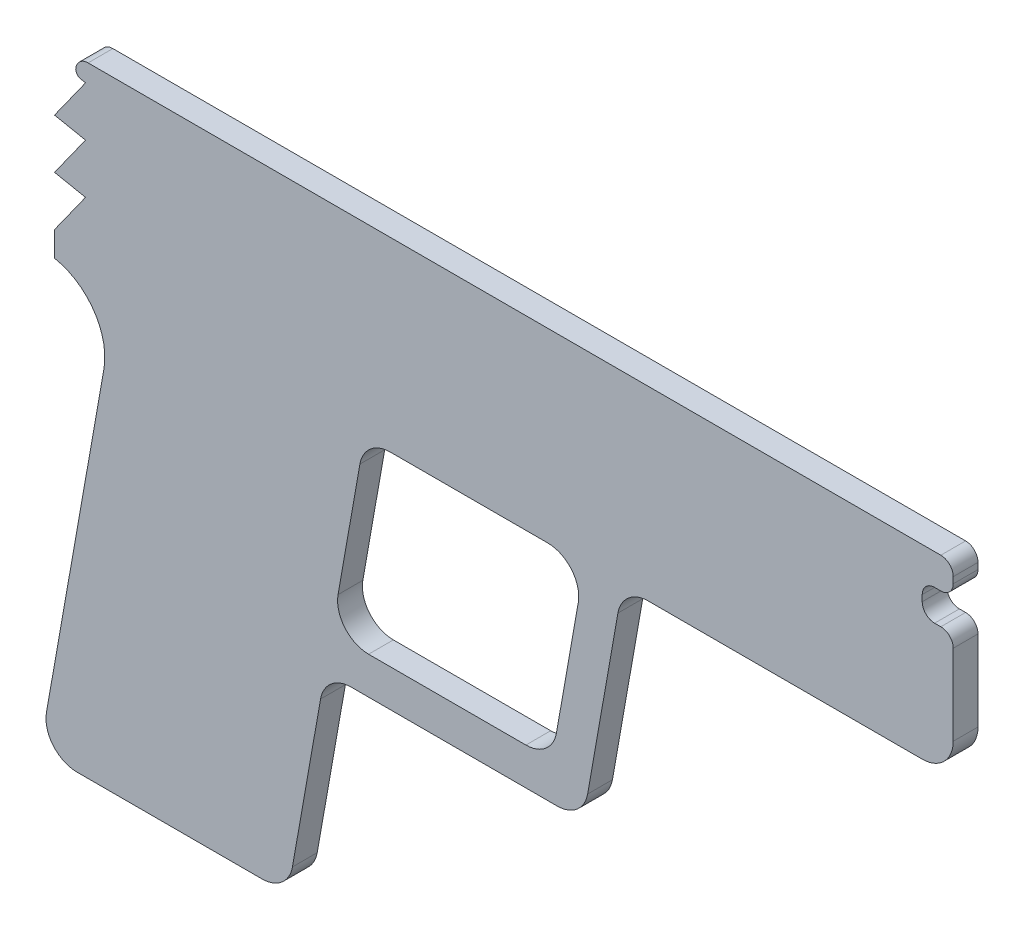
SolidWorks part; units mm, degrees
ref_plane "Front Plane" through (0, 0, 0) normal (0, 0, 1) x (1, 0, 0)
ref_plane "Top Plane" through (0, 0, 0) normal (0, 1, 0) x (1, 0, 0)
ref_plane "Right Plane" through (0, 0, 0) normal (1, 0, 0) x (0, 0, -1)
sketch "Sketch1" plane through (0, 0, 0) normal (0, 0, 1) x (1, 0, 0)
  line L0 (10, 0) -> (-2.3429, -70)
  line L1 (0, 0) -> (10, 0)
  line L2 (0, 0) -> (0, 30)
  line L3 (0, 30) -> (145, 30)
  line L4 (145, 0) -> (145, 20)
  line L5 (-2.3429, -70) -> (37.6571, -70)
  line L6 (37.6571, -70) -> (43.6522, -36)
  line L7 (44.7102, -30) -> (80.2501, -30)
  line L8 (145, 25) -> (140, 25)
  line L10 (145, 20) -> (140, 20)
  line L11 (140, 25) -> (140, 20)
  line L12 (80.2501, -30) -> (85.5399, 0)
  line L13 (43.6522, -36) -> (85.2847, -36)
  line L14 (85.2847, -36) -> (91.6325, 0)
  line L15 (85.2847, -36) -> (91.4488, -1.0419) construction
  line L16 (44.7102, -36) -> (85.2847, -36) construction
  line L17 (44.7102, -30) -> (50, 0)
  line L18 (50, 0) -> (85.5399, 0)
  line L19 (91.6325, 0) -> (145, 0)
  line L20 (145, 25) -> (145, 30)
  dimension "D1" = 145
  dimension "D2" = 30
  dimension "D3" = 80
  dimension "D4" = 10
  dimension "D5" = 40
  dimension "D6" = 5
  dimension "D7" = 5
  dimension "D8" = 5
  dimension "D10" = 35
  dimension "D11" = 30
  dimension "D12" = 70
  dimension "D9" = 6
extrude "Boss-Extrude1" add sketch "Sketch1" along normal blind 4
fillet "Fillet1" radius 10 1 edges at (10, 0, 2)
fillet "Fillet2" radius 5 10 edges at (-2.3429, -70, 2) (37.6571, -70, 2) (50, 0, 2) (44.7102, -30, 2) (43.6522, -36, 2) (85.5399, 0, 2) (91.6325, 0, 2) (80.2501, -30, 2) (85.2847, -36, 2) (145, 0, 2)
sketch "Sketch2" plane through (0, 0, 4) normal (0, 0, 1) x (1, 0, 0)
  line L0 (5, 30) -> (5, 0.7222) construction
  line L1 (145, 30) -> (0, 30) construction
  line L3 (0, 30) -> (0, 0) construction
  line L5 (0, 20) -> (0, 28)
  line L6 (0, 28) -> (5, 27)
  line L7 (5, 27) -> (0, 20)
  dimension "D1" = 5
  dimension "D2" = 1
  dimension "D3" = 2
  dimension "D4" = 8
extrude "Cut-Extrude1" cut sketch "Sketch2" against normal blind 4
pattern_linear "LPattern1" count 3 spacing 8 along (0, -1, 0) of "Cut-Extrude1"
fillet "Fillet3" radius 2 4 edges at (145, 20, 2) (145, 25, 2) (140, 25, 2) (140, 20, 2)
fillet "Fillet4" radius 2 1 edges at (145, 30, 2)
sketch "Sketch3" plane through (0, 0, 4) normal (0, 0, 1) x (1, 0, 0)
  line L0 (3.4106, 27.3179) -> (3.4106, 32.703)
  line L1 (5, 27) -> (0, 28) construction
  line L2 (3.4106, 32.703) -> (-2.245, 32.703)
  line L3 (-2.245, 32.703) -> (-2.245, 26.1999)
  line L4 (-2.245, 26.1999) -> (3.4106, 27.3179)
extrude "Cut-Extrude2" cut sketch "Sketch3" against normal blind 10
fillet "Fillet5" radius 2 1 edges at (3.4106, 30, 2)
fillet "Fillet6" radius 1 1 edges at (3.4106, 27.3179, 2)
